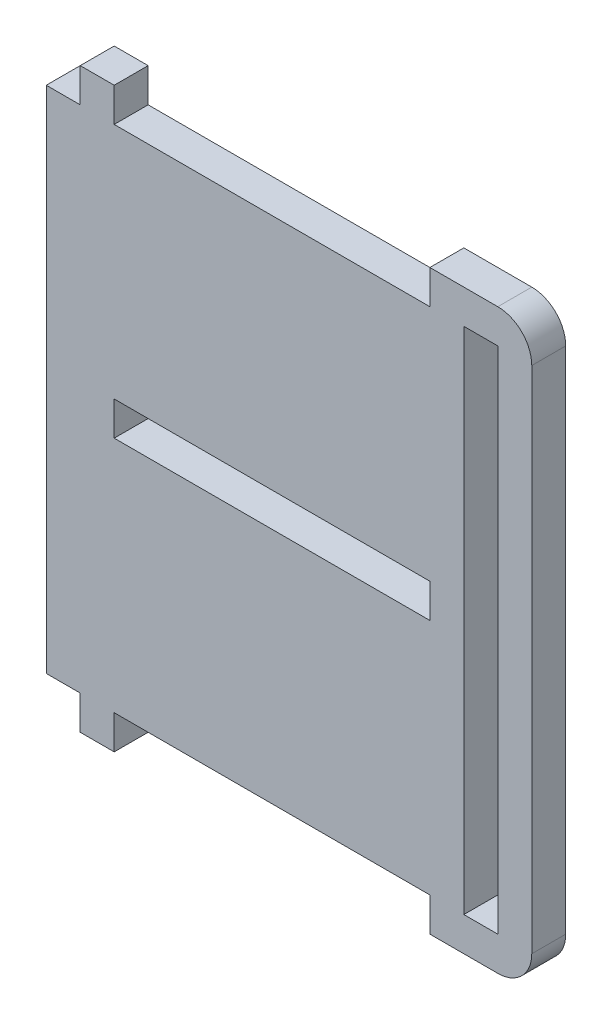
SolidWorks part; units mm, degrees
ref_plane "Front Plane" through (0, 0, 0) normal (0, 0, 1) x (1, 0, 0)
ref_plane "Top Plane" through (0, 0, 0) normal (0, 1, 0) x (1, 0, 0)
ref_plane "Right Plane" through (0, 0, 0) normal (1, 0, 0) x (0, 0, -1)
sketch "Sketch1" plane through (0, 0, 0) normal (0, 0, 1) x (1, 0, 0)
  line L1 (-36.4109, 0) -> (-30.0609, 0)
  line L2 (-36.4109, 0) -> (-36.4109, 6.35)
  line L3 (-36.4109, 107.95) -> (-30.0609, 107.95)
  line L4 (48.0139, 6.35) -> (48.0139, 101.6)
  line L5 (-36.4109, 6.35) -> (-42.7609, 6.35)
  line L7 (-36.4109, 101.6) -> (-42.7609, 101.6)
  line L8 (-42.7609, 6.35) -> (-42.7609, 101.6)
  line L9 (28.9639, 107.95) -> (41.6639, 107.95)
  line L10 (28.9639, 0) -> (41.6639, 0)
  line L11 (-36.4109, 101.6) -> (-36.4109, 107.95)
  line L12 (-30.0609, 101.6) -> (28.9639, 101.6)
  line L13 (28.9639, 101.6) -> (28.9639, 107.95)
  line L14 (28.9639, 107.95) -> (-30.0609, 107.95)
  line L15 (-30.0609, 107.95) -> (-30.0609, 101.6)
  line L16 (-30.0609, 101.6) -> (28.9639, 101.6)
  line L17 (28.9639, 101.6) -> (28.9639, 107.95)
  line L19 (-30.0609, 107.95) -> (-30.0609, 101.6)
  line L20 (-30.0609, 50.8) -> (28.9639, 50.8)
  line L21 (28.9639, 50.8) -> (28.9639, 57.15)
  line L22 (28.9639, 57.15) -> (-30.0609, 57.15)
  line L23 (-30.0609, 57.15) -> (-30.0609, 50.8)
  line L24 (-30.0609, 50.8) -> (28.9639, 50.8)
  line L25 (28.9639, 50.8) -> (28.9639, 57.15)
  line L26 (28.9639, 57.15) -> (-30.0609, 57.15)
  line L27 (-30.0609, 57.15) -> (-30.0609, 50.8)
  line L28 (-30.0609, 0) -> (28.9639, 0)
  line L29 (28.9639, 0) -> (28.9639, 6.35)
  line L30 (28.9639, 6.35) -> (-30.0609, 6.35)
  line L31 (-30.0609, 6.35) -> (-30.0609, 0)
  line L33 (28.9639, 0) -> (28.9639, 6.35)
  line L34 (28.9639, 6.35) -> (-30.0609, 6.35)
  line L35 (-30.0609, 6.35) -> (-30.0609, 0)
  line L37 (35.3139, 101.6) -> (35.3139, 6.35)
  line L38 (35.3139, 6.35) -> (41.6639, 6.35)
  line L39 (41.6639, 6.35) -> (41.6639, 101.6)
  line L40 (41.6639, 101.6) -> (35.3139, 101.6)
  line L41 (35.3139, 101.6) -> (35.3139, 6.35)
  line L42 (35.3139, 6.35) -> (41.6639, 6.35)
  line L43 (41.6639, 6.35) -> (41.6639, 101.6)
  line L44 (41.6639, 101.6) -> (35.3139, 101.6)
  arc A0 (41.6639, 107.95) -> (48.0139, 101.6) centre (41.6639, 101.6) cw
  arc A1 (41.6639, 0) -> (48.0139, 6.35) centre (41.6639, 6.35) ccw
  dimension "D1" = 6.35
  dimension "D2" = 0
  dimension "D3" = 0
  dimension "D4" = 0
  dimension "D7" = 0
extrude "Boss-Extrude1" add sketch "Sketch1" along normal blind 6.35
